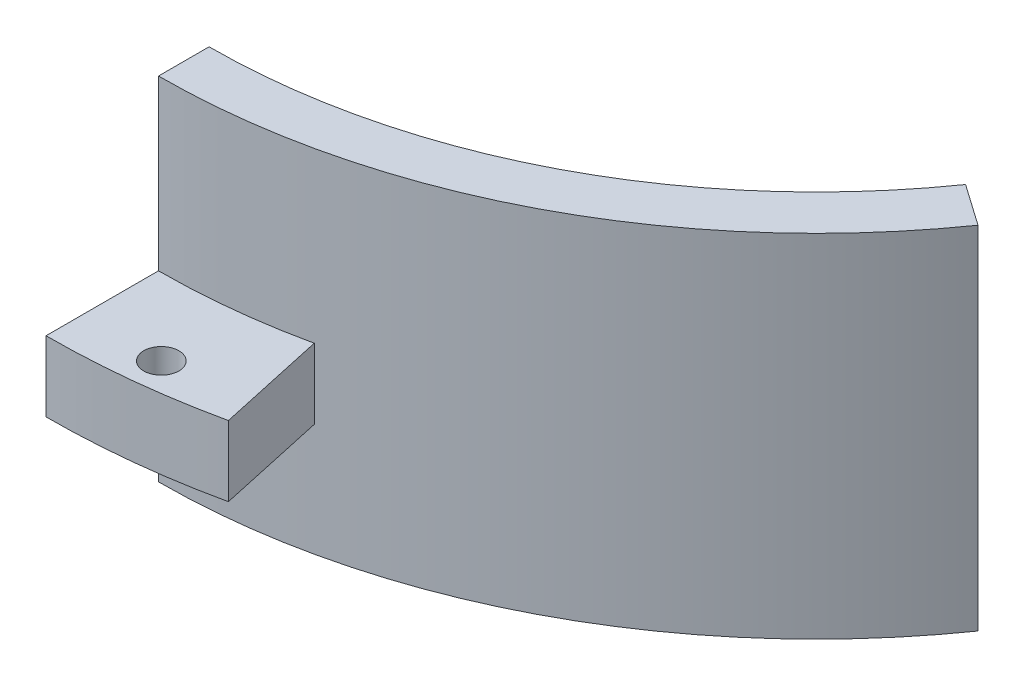
SolidWorks part; units mm, degrees
ref_plane "Front Plane" through (0, 0, 0) normal (0, 0, 1) x (1, 0, 0)
ref_plane "Top Plane" through (0, 0, 0) normal (0, 1, 0) x (1, 0, 0)
ref_plane "Right Plane" through (0, 0, 0) normal (1, 0, 0) x (0, 0, -1)
sketch "Sketch2" plane through (0, 0, 0) normal (0, 1, 0) x (1, 0, 0)
  line L0 (0, -46.8) -> (0, -43.2)
  line L1 (38.3363, -26.8434) -> (35.3874, -24.7785)
  line L2 (0, 0) -> (35.3874, -24.7785) construction
  circle A0 centre (0, 0) radius 46.8
  circle A1 centre (0, 0) radius 43.2
  dimension "D1" = 93.6
  dimension "D3" = 55
  dimension "D2" = 3.6
extrude "Boss-Extrude1" add sketch "Sketch2" along normal blind 25 contours A1 L0 A0 L1 region at (20.0007, 0, 38.421)
sketch "Sketch3" plane through (0, 25, 0) normal (0, 1, 0) x (1, 0, 0)
  line L0 (0, -43.2) -> (0, -40)
  line L1 (35.3874, -24.7785) -> (32.7661, -22.9431)
  line L2 (38.3363, -26.8434) -> (35.3874, -24.7785) construction
  circle A0 centre (0, 0) radius 40
  circle A2 centre (0, 0) radius 44.8
  arc M6 (35.3874, -24.7785) -> (0, -43.2) centre (0, 0) cw
  dimension "D1" = 80
  dimension "D2" = 89.6
extrude "Boss-Extrude2" add sketch "Sketch3" against normal blind 13 from offset 6 contours A0 L0 L1 M6 region at (18.4888, 25, 35.5166) offset against normal yes
sketch "Sketch4" plane through (0, 25, 0) normal (0, 1, 0) x (1, 0, 0)
  line L0 (0, -46.8) -> (0, -54.8)
  line L1 (10, -45.7191) -> (11.7094, -53.5344)
  line L2 (0, 0) -> (10, -45.7191) construction
  circle A0 centre (0, 0) radius 54.8
  arc A2 (0, -46.8) -> (38.3363, -26.8434) centre (0, 0) ccw construction
  circle A3 centre (0, 0) radius 46.8
  arc M7 (0, -46.8) -> (38.3363, -26.8434) centre (0, 0) ccw
  dimension "D1" = 8
  dimension "D2" = 10
extrude "Boss-Extrude3" add sketch "Sketch4" against normal blind 5 from offset 12 contours L0 A0 L1 M7 region at (5.4597, 25, 50.5125) offset against normal yes
sketch "Sketch5" plane through (0, 13, 0) normal (0, 1, 0) x (1, 0, 0)
  line L0 (5.0291, -46.529) -> (5.8888, -54.4827) construction
  circle A0 centre (5.647, -52.2457) radius 1.25
  arc A1 (0, -46.8) -> (10, -45.7191) centre (0, 0) ccw construction
  arc A2 (0, -54.8) -> (11.7094, -53.5344) centre (0, 0) ccw construction
  dimension "D1" = 2.5
  dimension "D2" = 2.25
extrude "M3-tap-hole" cut sketch "Sketch5" against normal up to next
sketch "Sketch6" plane through (0, 19, 0) normal (0, 1, 0) x (1, 0, 0)
  line L0 (0, -40) -> (0, -43)
  line L1 (0, -43.2) -> (0, -40) construction
  line L2 (0, -43) -> (5, -39.6863)
  arc A0 (0, -40) -> (32.7661, -22.9431) centre (0, 0) ccw construction
  arc A1 (0, -40) -> (5, -39.6863) centre (0, 0) ccw
  dimension "D1" = 3
  dimension "D2" = 5
extrude "Cut-Extrude1" cut sketch "Sketch6" against normal up to next
